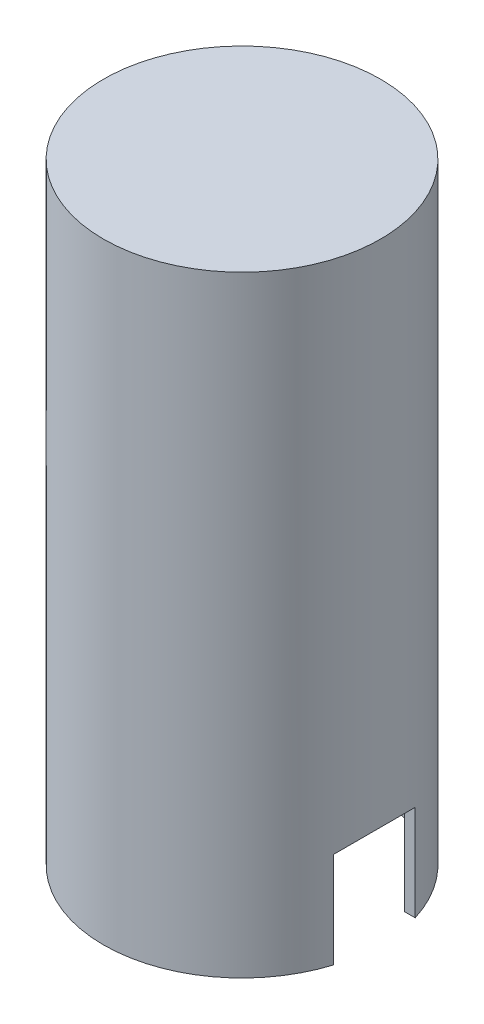
SolidWorks part; units mm, degrees
ref_plane "Front Plane" through (0, 0, 0) normal (0, 0, 1) x (1, 0, 0)
ref_plane "Top Plane" through (0, 0, 0) normal (0, 1, 0) x (1, 0, 0)
ref_plane "Right Plane" through (0, 0, 0) normal (1, 0, 0) x (0, 0, -1)
sketch "Sketch3" plane through (0, 0, 0) normal (0, 1, 0) x (1, 0, 0)
  circle A0 centre (0, 0) radius 68
  dimension "D1" = 136
extrude "Boss-Extrude1" add sketch "Sketch3" along normal blind 300
ref_axis "Axis1" through (0, 300, 0) along (0, -1, 0)
shell "Shell1" thickness 5 removed face at (0, 0, 68)
sketch "Sketch8" plane through (0, 0, 0) normal (0, 0, 1) x (1, 0, 0)
  line L0 (-68, 0) -> (-58, 0)
  line L1 (-68, 0) -> (68, 0) construction
  line L2 (-58, 0) -> (-58, 40)
  line L4 (-68, 300) -> (-68, 0) construction
  line L5 (-68, 50) -> (-68, 0)
  line L6 (-58, 40) -> (-68, 50)
  line L7 (0, -74.8) -> (0, 74.8) construction
  line L8 (68, 0) -> (58, 0)
  line L9 (58, 0) -> (58, 40)
  line L10 (58, 40) -> (68, 50)
  line L11 (68, 50) -> (68, 0)
  dimension "D1" = 10
  dimension "D2" = 50
  dimension "D3" = 40
extrude "Cut-Extrude3" cut sketch "Sketch8" against normal blind 20 and the other way blind 20
